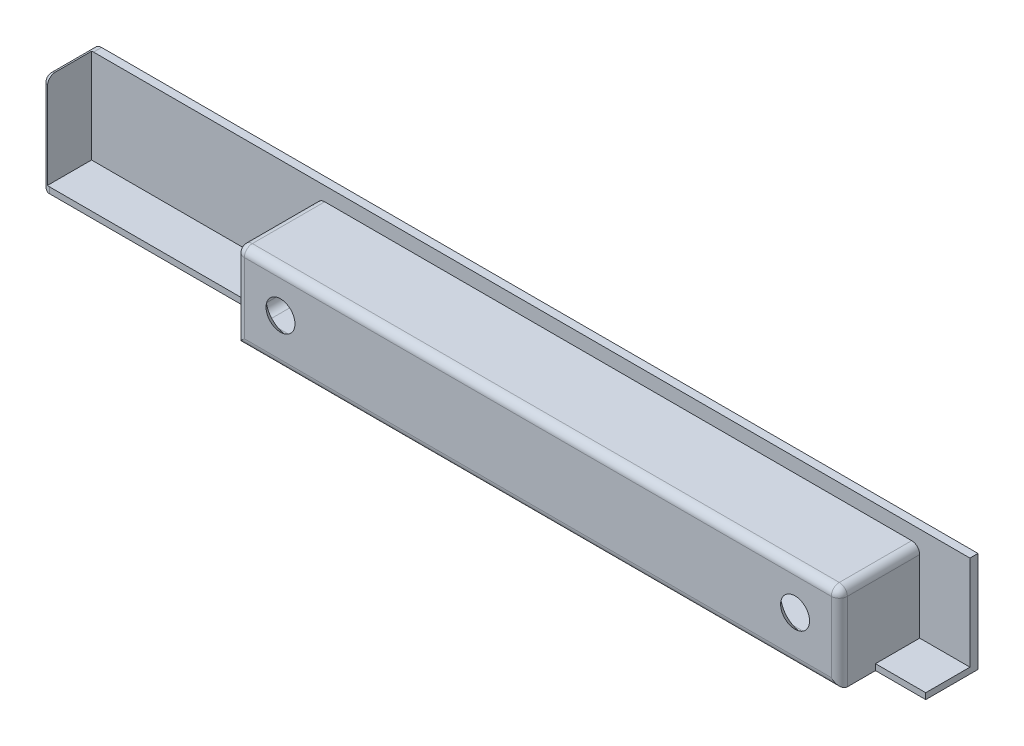
SolidWorks part; units mm, degrees
ref_plane "Alzado" through (0, 0, 0) normal (0, 0, 1) x (1, 0, 0)
ref_plane "Planta" through (0, 0, 0) normal (0, 1, 0) x (1, 0, 0)
ref_plane "Vista lateral" through (0, 0, 0) normal (1, 0, 0) x (0, 0, -1)
sketch "Croquis1" plane through (0, 0, 0) normal (0, 0, 1) x (1, 0, 0)
  line L1 (-239.5449, 63.6842) -> (-19.5449, 63.6842)
  line L2 (-239.5449, 63.6842) -> (-239.5449, 38.6842)
  line L3 (-239.5449, 38.6842) -> (-19.5449, 38.6842)
  line L4 (-19.5449, 63.6842) -> (-19.5449, 38.6842)
  dimension "D1" = 220
  dimension "D2" = 25
extrude "Saliente-Extruir1" add sketch "Croquis1" along normal blind 2
sketch "Croquis3" plane through (0, 0, 2) normal (0, 0, 1) x (1, 0, 0)
  line L0 (-239.5449, 63.6842) -> (-239.5449, 38.6842)
  line L1 (-239.5449, 38.6842) -> (-180.5449, 38.6842)
  line L2 (-239.5449, 38.6842) -> (-19.5449, 38.6842) construction
  line L3 (-180.5449, 38.6842) -> (-180.5449, 58.6842)
  line L4 (-180.5449, 58.6842) -> (-33.5449, 58.6842)
  line L5 (-33.5449, 58.6842) -> (-33.5449, 38.6842)
  line L6 (-33.5449, 38.6842) -> (-19.5449, 38.6842)
  line L7 (-19.5449, 38.6842) -> (-19.5449, 40.1842)
  line L8 (-19.5449, 38.6842) -> (-19.5449, 63.6842) construction
  line L9 (-19.5449, 40.1842) -> (-32.0449, 40.1842)
  line L10 (-32.0449, 40.1842) -> (-32.0449, 60.1842)
  line L11 (-32.0449, 60.1842) -> (-182.0449, 60.1842)
  line L12 (-182.0449, 60.1842) -> (-182.0449, 40.1842)
  line L13 (-182.0449, 40.1842) -> (-238.0449, 40.1842)
  line L14 (-238.0449, 40.1842) -> (-238.0449, 63.6842)
  line L15 (-19.5449, 63.6842) -> (-239.5449, 63.6842) construction
  line L16 (-238.0449, 63.6842) -> (-239.5449, 63.6842)
extrude "Saliente-Extruir2" add sketch "Croquis3" along normal blind 11
sketch "Croquis4" plane through (0, 0, 13) normal (0, 0, 1) x (1, 0, 0)
  line L0 (-182.0449, 40.1842) -> (-180.5449, 40.1842)
  line L1 (-180.5449, 38.6842) -> (-180.5449, 58.6842) construction
  line L2 (-180.5449, 40.471) -> (-180.5449, 58.6842)
  line L3 (-180.5449, 58.6842) -> (-33.5449, 58.6842)
  line L4 (-33.5449, 58.6842) -> (-33.5449, 40.471)
  line L5 (-33.5449, 58.6842) -> (-33.5449, 38.6842) construction
  line L7 (-32.0449, 40.1842) -> (-32.0449, 60.1842) construction
  line L8 (-32.0449, 40.471) -> (-32.0449, 60.1842)
  line L9 (-32.0449, 60.1842) -> (-182.0449, 60.1842)
  line L10 (-182.0449, 60.1842) -> (-182.0449, 40.1842)
  line L11 (-180.5449, 40.1842) -> (-180.5449, 40.471)
  line L12 (-32.0449, 40.1842) -> (-33.5449, 40.1842)
  line L13 (-33.5449, 40.1842) -> (-33.5449, 40.471)
  line L14 (-32.0449, 40.1842) -> (-32.0449, 40.471)
extrude "Saliente-Extruir3" add sketch "Croquis4" along normal blind 7
sketch "Croquis5" plane through (0, 0, 20) normal (0, 0, 1) x (1, 0, 0)
  line L1 (-182.0449, 60.1842) -> (-32.0449, 60.1842)
  line L2 (-182.0449, 60.1842) -> (-182.0449, 40.1842)
  line L3 (-182.0449, 40.1842) -> (-32.0449, 40.1842)
  line L4 (-32.0449, 60.1842) -> (-32.0449, 40.1842)
extrude "Saliente-Extruir4" add sketch "Croquis5" along normal blind 2
fillet "Redondeo2" radius 2 1 edges at (-239.5449, 63.6842, 6.5)
fillet "Redondeo3" radius 2 2 edges at (-239.5449, 50.1842, 13) (-239.1261, 62.909, 13)
fillet "Redondeo4" radius 2 1 edges at (-239.5449, 38.6842, 5.5) tangent propagation no
sketch "Croquis7" plane through (0, 0, 2) normal (0, 0, 1) x (1, 0, 0)
  line L1 (-180.5449, 58.6842) -> (-33.5449, 58.6842)
  line L2 (-180.5449, 58.6842) -> (-180.5449, 38.6842)
  line L3 (-180.5449, 38.6842) -> (-33.5449, 38.6842)
  line L4 (-33.5449, 58.6842) -> (-33.5449, 38.6842)
extrude "Cortar-Extruir1" cut sketch "Croquis7" against normal up to vertex (2 mm away) up to point (-19.5449, 38.6842, 0)
sketch "Croquis10" plane through (0, 0, 22) normal (0, 0, 1) x (1, 0, 0)
  line L2 (-182.0449, 40.1842) -> (-32.0449, 40.1842)
  line L3 (-182.0449, 40.1842) -> (-182.0449, 38.6842)
  line L4 (-182.0449, 38.6842) -> (-32.0449, 38.6842)
  line L7 (-32.0449, 40.1842) -> (-32.0449, 38.6842)
  dimension "D1" = 1.5
extrude "Saliente-Extruir8" add sketch "Croquis10" against normal blind 15
sketch "Croquis11" plane through (0, 0, 22) normal (0, 0, 1) x (1, 0, 0)
  line L0 (-32.0449, 60.1842) -> (-182.0449, 60.1842) construction
  line L1 (-182.0449, 60.1842) -> (-182.0449, 38.6842) construction
  circle A0 centre (-171.0449, 50.1842) radius 2.25
  circle A1 centre (-43.0449, 50.1842) radius 2.25
  dimension "D1" = 10
  dimension "D3" = 128
  dimension "D2" = 11
  dimension "D4" = 10
extrude "Cortar-Extruir2" cut sketch "Croquis11" against normal blind 15
hole_wizard "Refrentado para tornillo tapón con cabeza plana de clavija de M51" positions "Croquis13" profile "Croquis12" countersink size "M5" standard "Ansi Metric" end condition through all
sketch "Croquis13" plane through (0, 0, 20) normal (0, 0, -1) x (-1, 0, 0)
  point P0 (171.0449, 50.1842)
  point P3 (43.0449, 50.1842)
sketch "Croquis12" plane through (-171.0449, 50.1842, 20) normal (1, 0, 0) x (0, 1, 0)
  line L0 (0, 0) -> (0, 2)
  line L1 (0, 2) -> (2.9, 2)
  line L2 (2.9, 2) -> (2.9, 2.7)
  line L3 (2.9, 2.7) -> (5.6, 0)
  line L5 (5.6, 0) -> (0, 0)
  line L6 (-2.9, 2.7) -> (-5.6, 0) construction
  line L11 (0, -6.35) -> (0, 107.95) construction
  dimension "Diámetro de taladro hasta el siguiente" = 5.8
  dimension "Profundidad de taladro hasta el siguiente" = 2
  dimension "Diámetro de avellanado cercano" = 11.2
  dimension "Ángulo de avellanado cercano" = 90
fillet "Redondeo5" radius 2 6 edges at (-32.0449, 60.1842, 12) (-182.0449, 60.1842, 12) (-107.0449, 38.6842, 22) (-32.0449, 49.4342, 22) (-107.0449, 60.1842, 22) (-182.0449, 49.4342, 22)
sketch "Croquis14" plane through (0, 0, 20) normal (0, 0, -1) x (-1, 0, 0)
  line L0 (180.5449, 40.1842) -> (180.5449, 58.6842) construction
  line L1 (33.5449, 40.1842) -> (180.5449, 40.1842)
  line L2 (33.5449, 40.1842) -> (33.5449, 43.1842)
  line L3 (33.5449, 43.1842) -> (180.5449, 43.1842)
  line L4 (180.5449, 40.1842) -> (180.5449, 43.1842)
  dimension "D1" = 3
extrude "Saliente-Extruir9" add sketch "Croquis14" along normal up to surface (13 mm away) up to face at (-107.0449, 39.4342, 7)
fillet "Redondeo6" radius 2 3 edges at (-180.5449, 43.1842, 13.5) (-107.0449, 43.1842, 20) (-33.5449, 43.1842, 13.5)
